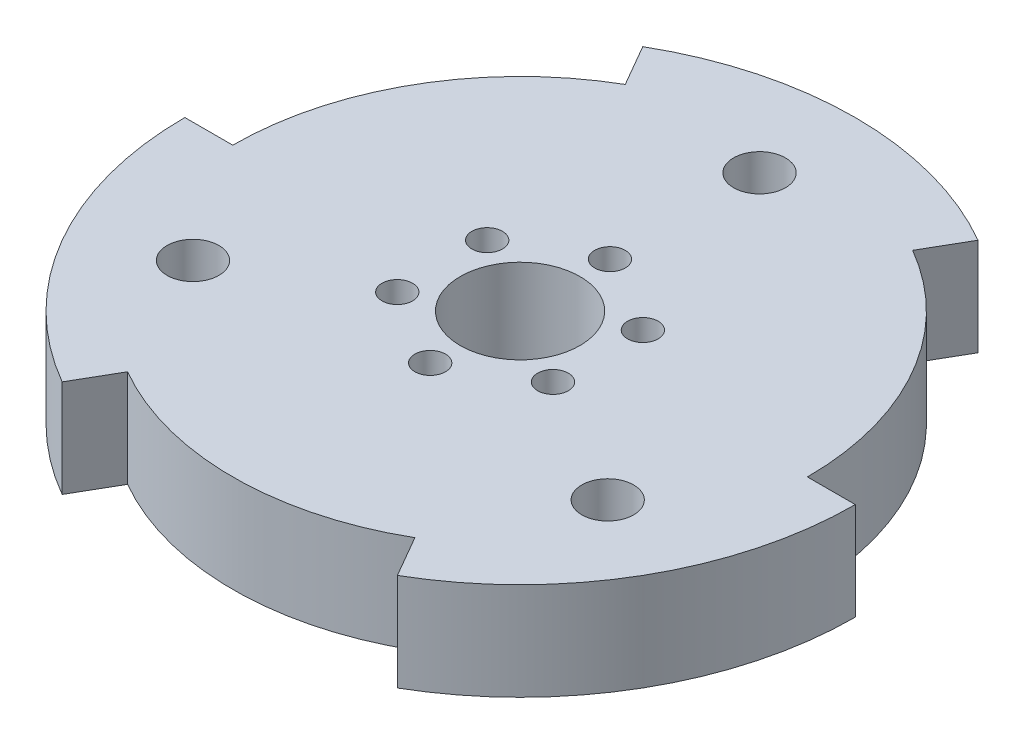
SolidWorks part; units mm, degrees
ref_plane "Front Plane" through (0, 0, 0) normal (0, 0, 1) x (1, 0, 0)
ref_plane "Top Plane" through (0, 0, 0) normal (0, 1, 0) x (1, 0, 0)
ref_plane "Right Plane" through (0, 0, 0) normal (1, 0, 0) x (0, 0, -1)
sketch "Sketch1" plane through (0, 0, 0) normal (0, 1, 0) x (1, 0, 0)
  line L0 (0, 0) -> (0, 35.4208) construction
  line L1 (-20, -20) -> (20, -20)
  line L2 (-20, -20) -> (-20, 20)
  line L3 (-20, 20) -> (20, 20)
  line L4 (20, -20) -> (20, 20)
  line L5 (-20, -20) -> (20, 20) construction
  line L6 (-20, 20) -> (20, -20) construction
  line L7 (17.5, 30.3109) -> (15, 25.9808)
  line L8 (-17.5, 30.3109) -> (-15, 25.9808)
  line L9 (17.5, -30.3109) -> (15, -25.9808)
  line L10 (35, 0) -> (30, 0)
  line L11 (-35, 0) -> (-30, 0)
  line L12 (-17.5, -30.3109) -> (-15, -25.9808)
  circle A0 centre (0, 0) radius 6.25
  circle A1 centre (0, 25) radius 2.7073
  circle A2 centre (21.6506, -12.5) radius 2.7073
  circle A3 centre (-21.6506, -12.5) radius 2.7073
  circle A4 centre (0, 0) radius 30
  arc A5 (17.5, 30.3109) -> (-17.5, 30.3109) centre (0, 0) ccw
  arc A6 (17.5, -30.3109) -> (35, 0) centre (0, 0) ccw
  arc A7 (-35, 0) -> (-17.5, -30.3109) centre (0, 0) ccw
  point P0 (0, 0)
  point P18 (0, 0)
  point P21 (0, 35)
  point P34 (0, 0)
  dimension "D2" = 12.5
  dimension "D6" = 60
  dimension "D7" = 5
  dimension "D8" = 35
  dimension "D9" = 3
  dimension "D1" = 25
  dimension "D3" = 40
  dimension "D4" = 40
  dimension "D5" = 3
extrude "Boss-Extrude1" add sketch "Sketch1" along normal blind 10.18 contours L11 A7 L12 A4 | L9 A6 L10 A4 | L7 A5 L8 A4 | L2 A3 | L4 A2 | A1 | L2 A3 | L4 A2 | A0 | A4 region at (-21.9823, 0, 12.5) region at (-19.5694, 0, 12.5) region at (19.5694, 0, 12.5) region at (21.9823, 0, 12.5) region at (0, 0, -31.0964) region at (26.9303, 0, 15.5482) region at (-26.9303, 0, 15.5482) region at (0, 0, 0) region at (0, 0, -25)
sketch "Sketch5" [suppressed] plane through (0, 0, 0) normal (1, 0, 0) x (0, 0, -1)
  line L0 (-10.331, 15) -> (10.331, 0) construction
  line L1 (10, 5) -> (-10, 5)
  line L2 (10, 5) -> (10, 10)
  line L3 (10, 10) -> (-10, 10)
  line L4 (-10, 5) -> (-10, 10)
  line L5 (10, 5) -> (-10, 10) construction
  line L6 (10, 10) -> (-10, 5) construction
  line L7 (20, 7.5) -> (-20, 7.5) construction
  line L8 (20, 15) -> (20, 0) construction
  line L9 (-20, 15) -> (-20, 0) construction
  line L10 (-10.3541, 15) -> (-10.3078, 15) construction
  line L11 (-10.3541, 0) -> (20, 0) construction
  point P0 (0, 7.5)
  dimension "D1" = 20
  dimension "D2" = 5
sketch "Sketch3" [suppressed] plane through (0, 0, -20) normal (0, 0, -1) x (-1, 0, 0)
  line L3 (15.1539, 15) -> (15.1539, 3) construction
  line L4 (20, 15) -> (10.3078, 15) construction
  circle A0 centre (15.1539, 3) radius 1.6
  dimension "D2" = 3.2
  dimension "D1" = 12
sketch "Sketch2" [suppressed] plane through (0, 0, 20) normal (0, 0, 1) x (1, 0, 0)
  line L0 (0, 27.8717) -> (0, -11.9207) construction
  line L1 (20, 2) -> (10, 2)
  line L3 (10, 2) -> (10, 0)
  line L4 (-20, 0) -> (20, 0) construction
  line L5 (20, 15) -> (20, 0) construction
  circle A0 centre (10, 2) radius 1.6
  circle A1 centre (-10, 2) radius 1.6
  dimension "D3" = 3.2
  dimension "D1" = 10
  dimension "D2" = 2
sketch "Sketch6" plane through (0, 10.18, 0) normal (0, 1, 0) x (1, 0, 0)
  circle A9 centre (0, -9.385) radius 1.6
  circle A10 centre (-8.1276, -4.6925) radius 1.6
  circle A11 centre (-8.1276, 4.6925) radius 1.6
  circle A12 centre (0, 9.385) radius 1.6
  circle A13 centre (8.1276, 4.6925) radius 1.6
  circle A14 centre (8.1276, -4.6925) radius 1.6
  point P3 (0, 0)
  point P16 (0, 0)
  dimension "D2" = 9.385
  dimension "D1" = 3.2
  dimension "D3" = 9.385
extrude "Cut-Extrude1" cut sketch "Sketch6" along normal through all and the other way through all
fillet "Fillet2" [suppressed] radius 5
